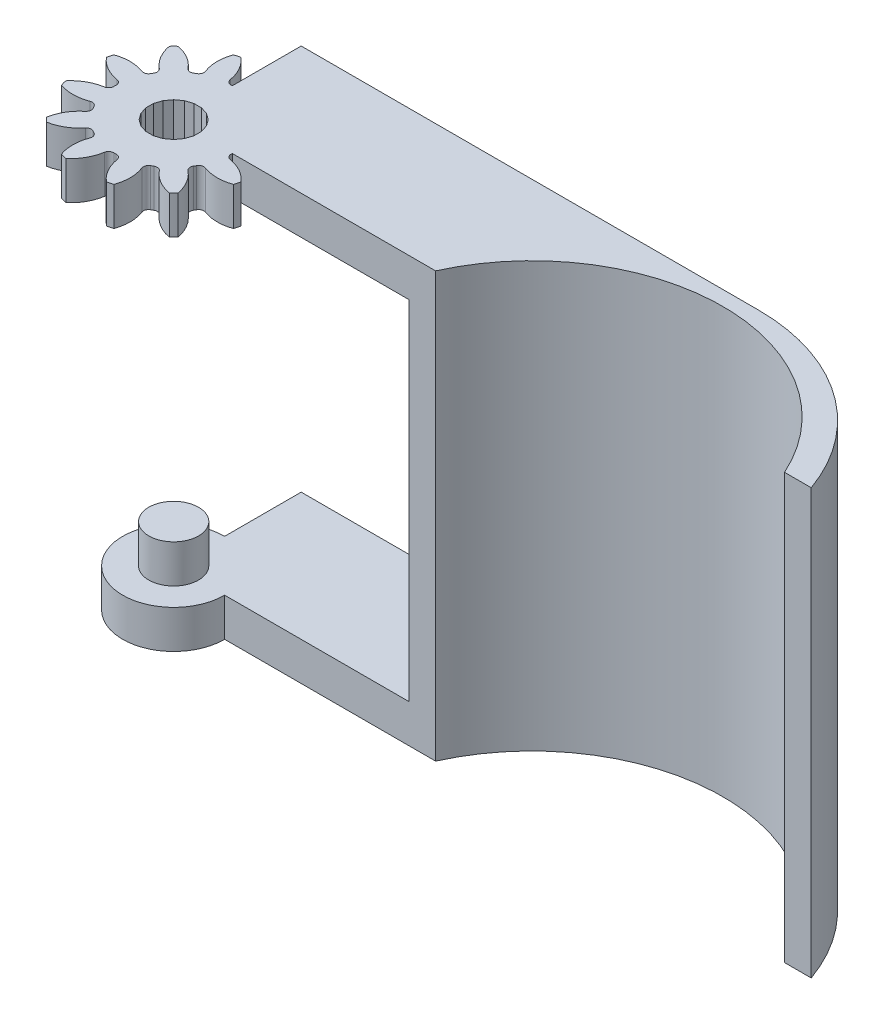
SolidWorks part; units mm, degrees
ref_plane "Front" through (0, 0, 0) normal (0, 0, 1) x (1, 0, 0)
ref_plane "Top" through (0, 0, 0) normal (0, 1, 0) x (1, 0, 0)
ref_plane "Right" through (0, 0, 0) normal (1, 0, 0) x (0, 0, -1)
sketch "Sketch1" plane through (0, 0, 0) normal (0, 1, 0) x (1, 0, 0)
  line L1 (0, 0) -> (50, 0)
  line L2 (0, 0) -> (0, 10)
  line L3 (0, 10) -> (50, 10)
  line L4 (50, 0) -> (50, 10)
  dimension "D1" = 50
  dimension "D2" = 10
extrude "Boss-Extrude2" add sketch "Sketch1" along normal mid plane 33.3 contours L1 L4 L3 L2
ref_plane "Plane1" through (0, 13.65, 0) normal (0, 1, 0) x (1, 0, 0)
ref_plane "Plane2" through (0, -13.65, 0) normal (0, -1, 0) x (-1, 0, 0)
sketch "Sketch2" plane through (0, 13.65, 0) normal (0, 1, 0) x (1, 0, 0)
  circle A0 centre (0, 0) radius 18.45
  dimension "D1" = 36.9
extrude "Cut-Extrude1" cut sketch "Sketch2" against normal up to surface (27.3 mm away) up to plane "Plane2"
sketch "Sketch3" plane through (0, 13.65, 0) normal (0, 1, 0) x (1, 0, 0)
  circle A0 centre (0, 0) radius 4
  dimension "D1" = 8
extrude "Boss-Extrude3" add sketch "Sketch3" along normal up to surface (3 mm away) contours A0 up to face at (25, 16.65, -5)
sketch "Sketch4" plane through (0, 13.65, 0) normal (0, -1, 0) x (1, 0, 0)
  line L1 (0.8694, 1.7063) -> (0.2996, 1.8914)
  line L2 (0.2996, 1.8914) -> (-0.2996, 1.8914)
  line L3 (-0.2996, 1.8914) -> (-0.8694, 1.7063)
  line L4 (-0.8694, 1.7063) -> (-1.3541, 1.3541)
  line L5 (-1.3541, 1.3541) -> (-1.7063, 0.8694)
  line L6 (-1.7063, 0.8694) -> (-1.8914, 0.2996)
  line L7 (-1.8914, 0.2996) -> (-1.8914, -0.2996)
  line L8 (-1.8914, -0.2996) -> (-1.7063, -0.8694)
  line L9 (-1.7063, -0.8694) -> (-1.3541, -1.3541)
  line L10 (-1.3541, -1.3541) -> (-0.8694, -1.7063)
  line L11 (-0.8694, -1.7063) -> (-0.2996, -1.8914)
  line L12 (-0.2996, -1.8914) -> (0.2996, -1.8914)
  line L13 (0.2996, -1.8914) -> (0.8694, -1.7063)
  line L14 (0.8694, -1.7063) -> (1.3541, -1.3541)
  line L15 (1.3541, -1.3541) -> (1.7063, -0.8694)
  line L16 (1.7063, -0.8694) -> (1.8914, -0.2996)
  line L17 (1.8914, -0.2996) -> (1.8914, 0.2996)
  line L18 (1.8914, 0.2996) -> (1.7063, 0.8694)
  line L19 (1.7063, 0.8694) -> (1.3541, 1.3541)
  line L20 (1.3541, 1.3541) -> (0.8694, 1.7063)
  circle A0 centre (0, 0) radius 1.915 construction
  circle A1 centre (0, 0) radius 1.8914 construction
  dimension "D1" = 3.83
extrude "Cut-Extrude2" cut sketch "Sketch4" against normal blind 3
sketch "Sketch5" plane through (0, -13.65, 0) normal (0, -1, 0) x (-1, 0, 0)
  arc A0 (-4, 0) -> (0, 4) centre (0, 0) ccw construction
  circle A1 centre (0, 0) radius 4
extrude "Boss-Extrude4" add sketch "Sketch5" along normal up to surface (3 mm away) contours A1 up to face at (25, -16.65, -5)
sketch "Sketch6" plane through (0, -13.65, 0) normal (0, 1, 0) x (1, 0, 0)
  circle A0 centre (0, 0) radius 1.95
  dimension "D1" = 3.9
extrude "Boss-Extrude5" add sketch "Sketch6" along normal blind 3 contours A0
sketch "Sketch7" plane through (0, 16.65, 0) normal (0, 1, 0) x (1, 0, 0)
  line L20 (1.3541, -1.3541) -> (1.7063, -0.8694)
  line L21 (0.8694, -1.7063) -> (1.3541, -1.3541)
  line L22 (0.2996, -1.8914) -> (0.8694, -1.7063)
  line L23 (-0.2996, -1.8914) -> (0.2996, -1.8914)
  line L24 (-0.8694, -1.7063) -> (-0.2996, -1.8914)
  line L25 (-1.3541, -1.3541) -> (-0.8694, -1.7063)
  line L26 (-1.7063, -0.8694) -> (-1.3541, -1.3541)
  line L27 (-1.8914, -0.2996) -> (-1.7063, -0.8694)
  line L28 (-1.8914, 0.2996) -> (-1.8914, -0.2996)
  line L29 (-1.7063, 0.8694) -> (-1.8914, 0.2996)
  line L30 (-1.3541, 1.3541) -> (-1.7063, 0.8694)
  line L31 (-0.8694, 1.7063) -> (-1.3541, 1.3541)
  line L32 (-0.2996, 1.8914) -> (-0.8694, 1.7063)
  line L33 (0.2996, 1.8914) -> (-0.2996, 1.8914)
  line L34 (0.8694, 1.7063) -> (0.2996, 1.8914)
  line L35 (1.3541, 1.3541) -> (0.8694, 1.7063)
  line L36 (1.7063, 0.8694) -> (1.3541, 1.3541)
  line L37 (1.8914, 0.2996) -> (1.7063, 0.8694)
  line L38 (1.8914, -0.2996) -> (1.8914, 0.2996)
  line L39 (1.7063, -0.8694) -> (1.8914, -0.2996)
  line L40 (1.3541, -1.3541) -> (1.7063, -0.8694)
  line L41 (0.8694, -1.7063) -> (1.3541, -1.3541)
  line L42 (0.2996, -1.8914) -> (0.8694, -1.7063)
  line L43 (-0.2996, -1.8914) -> (0.2996, -1.8914)
  line L44 (-0.8694, -1.7063) -> (-0.2996, -1.8914)
  line L45 (-1.3541, -1.3541) -> (-0.8694, -1.7063)
  line L46 (-1.7063, -0.8694) -> (-1.3541, -1.3541)
  line L47 (-1.8914, -0.2996) -> (-1.7063, -0.8694)
  line L48 (-1.8914, 0.2996) -> (-1.8914, -0.2996)
  line L49 (-1.7063, 0.8694) -> (-1.8914, 0.2996)
  line L50 (-1.3541, 1.3541) -> (-1.7063, 0.8694)
  line L51 (-0.8694, 1.7063) -> (-1.3541, 1.3541)
  line L52 (-0.2996, 1.8914) -> (-0.8694, 1.7063)
  line L53 (0.2996, 1.8914) -> (-0.2996, 1.8914)
  line L54 (0.8694, 1.7063) -> (0.2996, 1.8914)
  line L55 (1.3541, 1.3541) -> (0.8694, 1.7063)
  line L56 (1.7063, 0.8694) -> (1.3541, 1.3541)
  line L57 (1.8914, 0.2996) -> (1.7063, 0.8694)
  line L58 (1.8914, -0.2996) -> (1.8914, 0.2996)
  line L59 (1.7063, -0.8694) -> (1.8914, -0.2996)
  arc A144 (2.2209, -4.0267) -> (2.3768, -3.9367) centre (0, 0) ccw
  arc A145 (2.9017, -4.0276) -> (2.3768, -3.9367) centre (2.5868, -4.2847) ccw
  arc A146 (2.9017, -4.0276) -> (4.8112, -5.1532) centre (5.3812, -2.0035) ccw
  arc A147 (4.8112, -5.1532) -> (5.1532, -4.8112) centre (0, 0) ccw
  arc A148 (5.1532, -4.8112) -> (4.0276, -2.9017) centre (2.0035, -5.3812) ccw
  arc A149 (3.9367, -2.3768) -> (4.0276, -2.9017) centre (4.2847, -2.5868) ccw
  arc A150 (3.9367, -2.3768) -> (4.0267, -2.2209) centre (0, 0) ccw
  arc A151 (4.5268, -2.0372) -> (4.0267, -2.2209) centre (4.3826, -2.4172) ccw
  arc A152 (4.5268, -2.0372) -> (6.7432, -2.0572) centre (5.6621, 0.9555) ccw
  arc A153 (6.7432, -2.0572) -> (6.8684, -1.59) centre (0, 0) ccw
  arc A154 (6.8684, -1.59) -> (4.9389, -0.4991) centre (4.4257, -3.6585) ccw
  arc A155 (4.5977, -0.09) -> (4.9389, -0.4991) centre (5.004, -0.0979) ccw
  arc A156 (4.5977, -0.09) -> (4.5977, 0.09) centre (0, 0) ccw
  arc A157 (4.9389, 0.4991) -> (4.5977, 0.09) centre (5.004, 0.0979) ccw
  arc A158 (4.9389, 0.4991) -> (6.8684, 1.59) centre (4.4257, 3.6585) ccw
  arc A159 (6.8684, 1.59) -> (6.7432, 2.0572) centre (0, 0) ccw
  arc A160 (6.7432, 2.0572) -> (4.5268, 2.0372) centre (5.6621, -0.9555) ccw
  arc A161 (4.0267, 2.2209) -> (4.5268, 2.0372) centre (4.3826, 2.4172) ccw
  arc A162 (4.0267, 2.2209) -> (3.9367, 2.3768) centre (0, 0) ccw
  arc A163 (4.0276, 2.9017) -> (3.9367, 2.3768) centre (4.2847, 2.5868) ccw
  arc A164 (4.0276, 2.9017) -> (5.1532, 4.8112) centre (2.0035, 5.3812) ccw
  arc A165 (5.1532, 4.8112) -> (4.8112, 5.1532) centre (0, 0) ccw
  arc A166 (4.8112, 5.1532) -> (2.9017, 4.0276) centre (5.3812, 2.0035) ccw
  arc A167 (2.3768, 3.9367) -> (2.9017, 4.0276) centre (2.5868, 4.2847) ccw
  arc A168 (2.3768, 3.9367) -> (2.2209, 4.0267) centre (0, 0) ccw
  arc A169 (2.0372, 4.5268) -> (2.2209, 4.0267) centre (2.4172, 4.3826) ccw
  arc A170 (2.0372, 4.5268) -> (2.0572, 6.7432) centre (-0.9555, 5.6621) ccw
  arc A171 (2.0572, 6.7432) -> (1.59, 6.8684) centre (0, 0) ccw
  arc A172 (1.59, 6.8684) -> (0.4991, 4.9389) centre (3.6585, 4.4257) ccw
  arc A173 (0.09, 4.5977) -> (0.4991, 4.9389) centre (0.0979, 5.004) ccw
  arc A174 (0.09, 4.5977) -> (-0.09, 4.5977) centre (0, 0) ccw
  arc A175 (-0.4991, 4.9389) -> (-0.09, 4.5977) centre (-0.0979, 5.004) ccw
  arc A176 (-0.4991, 4.9389) -> (-1.59, 6.8684) centre (-3.6585, 4.4257) ccw
  arc A177 (-1.59, 6.8684) -> (-2.0572, 6.7432) centre (0, 0) ccw
  arc A178 (-2.0572, 6.7432) -> (-2.0372, 4.5268) centre (0.9555, 5.6621) ccw
  arc A179 (-2.2209, 4.0267) -> (-2.0372, 4.5268) centre (-2.4172, 4.3826) ccw
  arc A180 (-2.2209, 4.0267) -> (-2.3768, 3.9367) centre (0, 0) ccw
  arc A181 (-2.9017, 4.0276) -> (-2.3768, 3.9367) centre (-2.5868, 4.2847) ccw
  arc A182 (-2.9017, 4.0276) -> (-4.8112, 5.1532) centre (-5.3812, 2.0035) ccw
  arc A183 (-4.8112, 5.1532) -> (-5.1532, 4.8112) centre (0, 0) ccw
  arc A184 (-5.1532, 4.8112) -> (-4.0276, 2.9017) centre (-2.0035, 5.3812) ccw
  arc A185 (-3.9367, 2.3768) -> (-4.0276, 2.9017) centre (-4.2847, 2.5868) ccw
  arc A186 (-3.9367, 2.3768) -> (-4.0267, 2.2209) centre (0, 0) ccw
  arc A187 (-4.5268, 2.0372) -> (-4.0267, 2.2209) centre (-4.3826, 2.4172) ccw
  arc A188 (-4.5268, 2.0372) -> (-6.7432, 2.0572) centre (-5.6621, -0.9555) ccw
  arc A189 (-6.7432, 2.0572) -> (-6.8684, 1.59) centre (0, 0) ccw
  arc A190 (-6.8684, 1.59) -> (-4.9389, 0.4991) centre (-4.4257, 3.6585) ccw
  arc A191 (-4.5977, 0.09) -> (-4.9389, 0.4991) centre (-5.004, 0.0979) ccw
  arc A192 (-4.5977, 0.09) -> (-4.5977, -0.09) centre (0, 0) ccw
  arc A193 (-4.9389, -0.4991) -> (-4.5977, -0.09) centre (-5.004, -0.0979) ccw
  arc A194 (-4.9389, -0.4991) -> (-6.8684, -1.59) centre (-4.4257, -3.6585) ccw
  arc A195 (-6.8684, -1.59) -> (-6.7432, -2.0572) centre (0, 0) ccw
  arc A196 (-6.7432, -2.0572) -> (-4.5268, -2.0372) centre (-5.6621, 0.9555) ccw
  arc A197 (-4.0267, -2.2209) -> (-4.5268, -2.0372) centre (-4.3826, -2.4172) ccw
  arc A198 (-4.0267, -2.2209) -> (-3.9367, -2.3768) centre (0, 0) ccw
  arc A199 (-4.0276, -2.9017) -> (-3.9367, -2.3768) centre (-4.2847, -2.5868) ccw
  arc A200 (-4.0276, -2.9017) -> (-5.1532, -4.8112) centre (-2.0035, -5.3812) ccw
  arc A201 (-5.1532, -4.8112) -> (-4.8112, -5.1532) centre (0, 0) ccw
  arc A202 (-4.8112, -5.1532) -> (-2.9017, -4.0276) centre (-5.3812, -2.0035) ccw
  arc A203 (-2.3768, -3.9367) -> (-2.9017, -4.0276) centre (-2.5868, -4.2847) ccw
  arc A204 (-2.3768, -3.9367) -> (-2.2209, -4.0267) centre (0, 0) ccw
  arc A205 (-2.0372, -4.5268) -> (-2.2209, -4.0267) centre (-2.4172, -4.3826) ccw
  arc A206 (-2.0372, -4.5268) -> (-2.0572, -6.7432) centre (0.9555, -5.6621) ccw
  arc A207 (-2.0572, -6.7432) -> (-1.59, -6.8684) centre (0, 0) ccw
  arc A208 (-1.59, -6.8684) -> (-0.4991, -4.9389) centre (-3.6585, -4.4257) ccw
  arc A209 (-0.09, -4.5977) -> (-0.4991, -4.9389) centre (-0.0979, -5.004) ccw
  arc A210 (-0.09, -4.5977) -> (0.09, -4.5977) centre (0, 0) ccw
  arc A211 (0.4991, -4.9389) -> (0.09, -4.5977) centre (0.0979, -5.004) ccw
  arc A212 (0.4991, -4.9389) -> (1.59, -6.8684) centre (3.6585, -4.4257) ccw
  arc A213 (1.59, -6.8684) -> (2.0572, -6.7432) centre (0, 0) ccw
  arc A214 (2.0572, -6.7432) -> (2.0372, -4.5268) centre (-0.9555, -5.6621) ccw
  arc A215 (2.2209, -4.0267) -> (2.0372, -4.5268) centre (2.4172, -4.3826) ccw
  arc A216 (2.2209, -4.0267) -> (2.3768, -3.9367) centre (0, 0) ccw
  arc A217 (2.9017, -4.0276) -> (2.3768, -3.9367) centre (2.5868, -4.2847) ccw
  arc A218 (2.9017, -4.0276) -> (4.8112, -5.1532) centre (5.3812, -2.0035) ccw
  arc A219 (4.8112, -5.1532) -> (5.1532, -4.8112) centre (0, 0) ccw
  arc A220 (5.1532, -4.8112) -> (4.0276, -2.9017) centre (2.0035, -5.3812) ccw
  arc A221 (3.9367, -2.3768) -> (4.0276, -2.9017) centre (4.2847, -2.5868) ccw
  arc A222 (3.9367, -2.3768) -> (4.0267, -2.2209) centre (0, 0) ccw
  arc A223 (4.5268, -2.0372) -> (4.0267, -2.2209) centre (4.3826, -2.4172) ccw
  arc A224 (4.5268, -2.0372) -> (6.7432, -2.0572) centre (5.6621, 0.9555) ccw
  arc A225 (6.7432, -2.0572) -> (6.8684, -1.59) centre (0, 0) ccw
  arc A226 (6.8684, -1.59) -> (4.9389, -0.4991) centre (4.4257, -3.6585) ccw
  arc A227 (4.5977, -0.09) -> (4.9389, -0.4991) centre (5.004, -0.0979) ccw
  arc A228 (4.5977, -0.09) -> (4.5977, 0.09) centre (0, 0) ccw
  arc A229 (4.9389, 0.4991) -> (4.5977, 0.09) centre (5.004, 0.0979) ccw
  arc A230 (4.9389, 0.4991) -> (6.8684, 1.59) centre (4.4257, 3.6585) ccw
  arc A231 (6.8684, 1.59) -> (6.7432, 2.0572) centre (0, 0) ccw
  arc A232 (6.7432, 2.0572) -> (4.5268, 2.0372) centre (5.6621, -0.9555) ccw
  arc A233 (4.0267, 2.2209) -> (4.5268, 2.0372) centre (4.3826, 2.4172) ccw
  arc A234 (4.0267, 2.2209) -> (3.9367, 2.3768) centre (0, 0) ccw
  arc A235 (4.0276, 2.9017) -> (3.9367, 2.3768) centre (4.2847, 2.5868) ccw
  arc A236 (4.0276, 2.9017) -> (5.1532, 4.8112) centre (2.0035, 5.3812) ccw
  arc A237 (5.1532, 4.8112) -> (4.8112, 5.1532) centre (0, 0) ccw
  arc A238 (4.8112, 5.1532) -> (2.9017, 4.0276) centre (5.3812, 2.0035) ccw
  arc A239 (2.3768, 3.9367) -> (2.9017, 4.0276) centre (2.5868, 4.2847) ccw
  arc A240 (2.3768, 3.9367) -> (2.2209, 4.0267) centre (0, 0) ccw
  arc A241 (2.0372, 4.5268) -> (2.2209, 4.0267) centre (2.4172, 4.3826) ccw
  arc A242 (2.0372, 4.5268) -> (2.0572, 6.7432) centre (-0.9555, 5.6621) ccw
  arc A243 (2.0572, 6.7432) -> (1.59, 6.8684) centre (0, 0) ccw
  arc A244 (1.59, 6.8684) -> (0.4991, 4.9389) centre (3.6585, 4.4257) ccw
  arc A245 (0.09, 4.5977) -> (0.4991, 4.9389) centre (0.0979, 5.004) ccw
  arc A246 (0.09, 4.5977) -> (-0.09, 4.5977) centre (0, 0) ccw
  arc A247 (-0.4991, 4.9389) -> (-0.09, 4.5977) centre (-0.0979, 5.004) ccw
  arc A248 (-0.4991, 4.9389) -> (-1.59, 6.8684) centre (-3.6585, 4.4257) ccw
  arc A249 (-1.59, 6.8684) -> (-2.0572, 6.7432) centre (0, 0) ccw
  arc A250 (-2.0572, 6.7432) -> (-2.0372, 4.5268) centre (0.9555, 5.6621) ccw
  arc A251 (-2.2209, 4.0267) -> (-2.0372, 4.5268) centre (-2.4172, 4.3826) ccw
  arc A252 (-2.2209, 4.0267) -> (-2.3768, 3.9367) centre (0, 0) ccw
  arc A253 (-2.9017, 4.0276) -> (-2.3768, 3.9367) centre (-2.5868, 4.2847) ccw
  arc A254 (-2.9017, 4.0276) -> (-4.8112, 5.1532) centre (-5.3812, 2.0035) ccw
  arc A255 (-4.8112, 5.1532) -> (-5.1532, 4.8112) centre (0, 0) ccw
  arc A256 (-5.1532, 4.8112) -> (-4.0276, 2.9017) centre (-2.0035, 5.3812) ccw
  arc A257 (-3.9367, 2.3768) -> (-4.0276, 2.9017) centre (-4.2847, 2.5868) ccw
  arc A258 (-3.9367, 2.3768) -> (-4.0267, 2.2209) centre (0, 0) ccw
  arc A259 (-4.5268, 2.0372) -> (-4.0267, 2.2209) centre (-4.3826, 2.4172) ccw
  arc A260 (-4.5268, 2.0372) -> (-6.7432, 2.0572) centre (-5.6621, -0.9555) ccw
  arc A261 (-6.7432, 2.0572) -> (-6.8684, 1.59) centre (0, 0) ccw
  arc A262 (-6.8684, 1.59) -> (-4.9389, 0.4991) centre (-4.4257, 3.6585) ccw
  arc A263 (-4.5977, 0.09) -> (-4.9389, 0.4991) centre (-5.004, 0.0979) ccw
  arc A264 (-4.5977, 0.09) -> (-4.5977, -0.09) centre (0, 0) ccw
  arc A265 (-4.9389, -0.4991) -> (-4.5977, -0.09) centre (-5.004, -0.0979) ccw
  arc A266 (-4.9389, -0.4991) -> (-6.8684, -1.59) centre (-4.4257, -3.6585) ccw
  arc A267 (-6.8684, -1.59) -> (-6.7432, -2.0572) centre (0, 0) ccw
  arc A268 (-6.7432, -2.0572) -> (-4.5268, -2.0372) centre (-5.6621, 0.9555) ccw
  arc A269 (-4.0267, -2.2209) -> (-4.5268, -2.0372) centre (-4.3826, -2.4172) ccw
  arc A270 (-4.0267, -2.2209) -> (-3.9367, -2.3768) centre (0, 0) ccw
  arc A271 (-4.0276, -2.9017) -> (-3.9367, -2.3768) centre (-4.2847, -2.5868) ccw
  arc A272 (-4.0276, -2.9017) -> (-5.1532, -4.8112) centre (-2.0035, -5.3812) ccw
  arc A273 (-5.1532, -4.8112) -> (-4.8112, -5.1532) centre (0, 0) ccw
  arc A274 (-4.8112, -5.1532) -> (-2.9017, -4.0276) centre (-5.3812, -2.0035) ccw
  arc A275 (-2.3768, -3.9367) -> (-2.9017, -4.0276) centre (-2.5868, -4.2847) ccw
  arc A276 (-2.3768, -3.9367) -> (-2.2209, -4.0267) centre (0, 0) ccw
  arc A277 (-2.0372, -4.5268) -> (-2.2209, -4.0267) centre (-2.4172, -4.3826) ccw
  arc A278 (-2.0372, -4.5268) -> (-2.0572, -6.7432) centre (0.9555, -5.6621) ccw
  arc A279 (-2.0572, -6.7432) -> (-1.59, -6.8684) centre (0, 0) ccw
  arc A280 (-1.59, -6.8684) -> (-0.4991, -4.9389) centre (-3.6585, -4.4257) ccw
  arc A281 (-0.09, -4.5977) -> (-0.4991, -4.9389) centre (-0.0979, -5.004) ccw
  arc A282 (-0.09, -4.5977) -> (0.09, -4.5977) centre (0, 0) ccw
  arc A283 (0.4991, -4.9389) -> (0.09, -4.5977) centre (0.0979, -5.004) ccw
  arc A284 (0.4991, -4.9389) -> (1.59, -6.8684) centre (3.6585, -4.4257) ccw
  arc A285 (1.59, -6.8684) -> (2.0572, -6.7432) centre (0, 0) ccw
  arc A286 (2.0572, -6.7432) -> (2.0372, -4.5268) centre (-0.9555, -5.6621) ccw
  arc A287 (2.2209, -4.0267) -> (2.0372, -4.5268) centre (2.4172, -4.3826) ccw
  line M113 (0, 10) -> (0, 4)
  arc M114 (0, 4) -> (4, 0) centre (0, 0) ccw
  line M115 (4, 0) -> (50, 0)
  dimension "D1" = 0.1
  dimension "D2" = 0
extrude "Boss-Extrude6" add sketch "Sketch7" against normal up to surface (3 mm away) contours A287 A216 A217 A218 A219 A220 A221 A222 A223 A224 A225 A226 A227 A228 A246 A247 A248 A249 A250 A251 A252 A253 A254 A255 A256 A257 A258 A259 A260 A261 A262 A263 A264 A265 A266 A267 A268 A269 A270 A271 A272 A273 A274 A275 A276 A277 A278 A279 M115 M114 M113 region at (1.8534, 16.65, 4.1754) up to face at (0, 13.65, 0)
sketch "Sketch9" plane through (0, 13.65, 0) normal (0, -1, 0) x (1, 0, 0)
  line L0 (0, 0) -> (0, 3.18) construction
  line L1 (0, 3.18) -> (0, 3.38) construction
  circle A0 centre (0, 0) radius 2.98
  circle A1 centre (0, 0) radius 3.38
  point P5 (0, 2.98)
  dimension "D2" = 0.2
  dimension "D1" = 3.18
  dimension "D3" = 0.2
extrude "Cut-Extrude3" cut sketch "Sketch9" against normal blind 1
sketch "Sketch10" plane through (0, 16.65, 0) normal (0, 1, 0) x (1, 0, 0)
  line L0 (34.225, 0) -> (34.225, -6.15) construction
  line L1 (4.5986, 0) -> (50, 0) construction
  line L2 (50, 0) -> (18.45, 0) construction
  circle A0 centre (34.225, -6.15) radius 15
  point P7 (20.0785, 0)
  point P8 (18.1386, 0)
  point P11 (0, 0)
  dimension "D1" = 30
  dimension "D2" = 6.15
extrude "Cut-Extrude4" cut sketch "Sketch10" against normal through all contours A0
fillet "Fillet1" radius 15 1 edges at (50, 0, -10)
